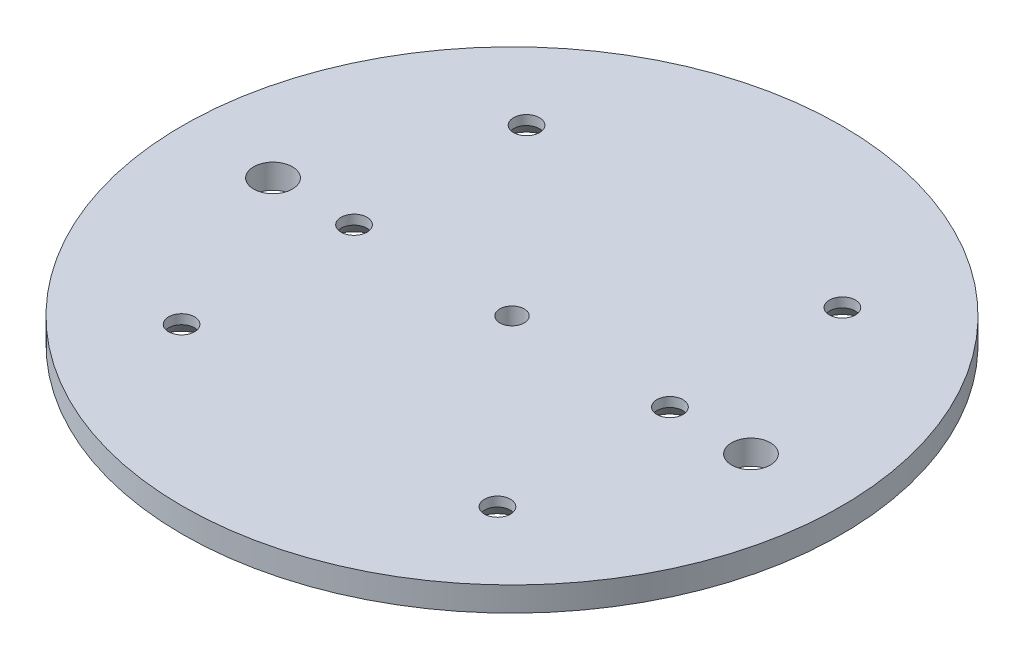
SolidWorks part; units mm, degrees
material "Malleable Cast Iron"
ref_plane "Front Plane" through (0, 0, 0) normal (0, 0, 1) x (1, 0, 0)
ref_plane "Top Plane" through (0, 0, 0) normal (0, 1, 0) x (1, 0, 0)
ref_plane "Right Plane" through (0, 0, 0) normal (1, 0, 0) x (0, 0, -1)
sketch "Sketch1" plane through (0, 0, 0) normal (0, 1, 0) x (1, 0, 0)
  circle A0 centre (0, 0) radius 85.725
  dimension "D1" = 171.45
extrude "Boss-Extrude1" add sketch "Sketch1" along normal blind 6.35
hole_wizard "3/8 Clearance Hole1" positions "Sketch6" profile "Sketch7" hole size "3/8" standard "ANSI Inch" end condition through all
sketch "Sketch6" plane through (0, 6.35, 0) normal (0, 1, 0) x (0.9997, 0, 0.0242)
  line L2 (54.3263, -144.7753) -> (48.6295, 90.1056) construction
  line L3 (-47.2438, -147.2388) -> (-52.9406, 87.6421) construction
  line L4 (-73.5114, -1.7829) -> (-50.7851, -1.2317) construction
  line L5 (50.7851, 1.2317) -> (73.5114, 1.7829) construction
  line L6 (-50.7851, -1.2317) -> (0, 0) construction
  circle A1 centre (0, 0) radius 73.533 construction
  point P0 (-62.1482, -1.5073)
  point P1 (62.1482, 1.5073)
sketch "Sketch7" plane through (-62.1665, 6.35, 0) normal (1, 0, 0) x (0, 0, 1)
  line L0 (0, 0) -> (0, 6.35)
  line L1 (0, 6.35) -> (5.0419, 6.35)
  line L2 (5.0419, 6.35) -> (5.0419, 0)
  line L5 (5.0419, 0) -> (0, 0)
  line L11 (0, -6.35) -> (0, 107.95) construction
  dimension "Thru Hole Dia." = 10.0838
  dimension "Thru Hole Depth" = 6.35
hole_wizard "1/4 (0.25) Clearance Dowel Hole1" positions "Sketch8" profile "Sketch9" hole size "1/4" standard "ANSI Inch" end condition through all
sketch "Sketch8" plane through (43.3774, 6.35, -259.2845) normal (0, 1, 0) x (0.9888, 0, -0.1489)
  point P0 (-81.5106, -249.9322)
sketch "Sketch9" plane through (0, 6.35, 0) normal (1, 0, 0) x (0, 0, 1)
  line L0 (0, 0) -> (0, 6.35)
  line L1 (0, 6.35) -> (3.175, 6.35)
  line L2 (3.175, 6.35) -> (3.175, 0)
  line L3 (3.175, 0) -> (0, 0)
  line L4 (0, -6.35) -> (0, 107.95) construction
  dimension "Thru Hole Dia." = 6.35
  dimension "Thru Hole Depth" = 6.35
hole_wizard "CSK for 1/4 Flat Head Socket Cap Screw1" positions "Sketch10" profile "Sketch11" countersink size "1/4" standard "ANSI Inch" end condition through all
sketch "Sketch10" plane through (43.3774, 0, -259.2845) normal (0, -1, 0) x (-0.9888, 0, 0.1489)
  line L4 (81.5106, -249.9322) -> (68.743, -165.1633) construction
  line L5 (-36.6218, 22.5662) -> (-17.3346, 22.5662) construction
  line L6 (-54.5349, -160.3265) -> (-35.2477, -160.3265) construction
  line L8 (81.5106, -249.9322) -> (-3.2583, -262.6998) construction
  circle A2 centre (81.5106, -249.9322) radius 73.533 construction
  circle A3 centre (81.5106, -249.9322) radius 60.833 construction
  point P0 (34.2025, -211.6882)
  point P1 (47.5661, -300.4141)
  point P14 (40.8843, -256.0512)
  point P19 (115.4551, -199.4502)
  point P20 (122.1369, -243.8132)
  point P21 (128.8187, -288.1761)
sketch "Sketch11" plane through (41.0845, 0, -44.8633) normal (1, 0, 0) x (0, 0, -1)
  line L0 (0, 0) -> (0, 6.35)
  line L1 (0, 6.35) -> (3.3782, 6.35)
  line L2 (3.3782, 6.35) -> (3.3782, 3.8716)
  line L3 (3.3782, 3.8716) -> (6.7437, 0)
  line L5 (6.7437, 0) -> (0, 0)
  line L6 (-3.3782, 3.8716) -> (-6.7437, 0) construction
  line L11 (0, -6.35) -> (0, 107.95) construction
  dimension "Thru Hole Dia." = 6.7564
  dimension "Thru Hole Depth" = 6.35
  dimension "Near C'Sink Dia." = 13.4874
  dimension "Near C'Sink Angle" = 82
equation "\"delta-z\" = 1.5"
equation "\"total-height\" = 3.28"
equation "\"mid-height\" = 1.5"
equation "\"jaw-width\" = 4"
equation "\"jaw-height\" = \"total-height\" - \"mid-height\""
equation "\"max-tube-diam\" = 3.5"
equation "\"v-block-notch-height\" = 1.5"
equation "\"v-block-notch-angle\" = 120"
equation "\"vise-mod-plate-thickness\"= .375"
equation "\"vise-mod-height\"= .5 * \"max-tube-diam\" + \"delta-z\""
equation "\"jaw-travel\" = 4.45"
equation "\"rib-top-width\" = 0.5"
equation "\"rib-side-width\" = 0.5"
equation "\"quarter-twenty-close-clearance\" = .257"
equation "\"box-way-width\" = 1.5"
equation "\"box-way-depth\" = 1.5"
equation "\"screw-OD\" = .625"
equation "\"screw-reduced-diam\" = .47"
equation "\"pressure-plate-OD\" = 6.75"
equation "\"D1@Sketch1\"=\"pressure-plate-OD\""
